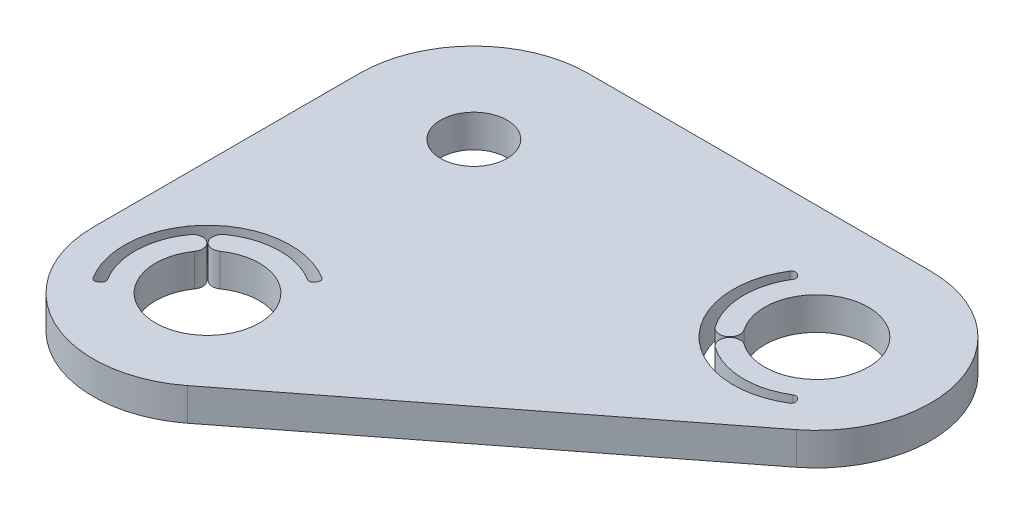
SolidWorks part; units mm, degrees
ref_plane "Front" through (0, 0, 0) normal (0, 0, 1) x (1, 0, 0)
ref_plane "Top" through (0, 0, 0) normal (0, 1, 0) x (1, 0, 0)
ref_plane "Right" through (0, 0, 0) normal (1, 0, 0) x (0, 0, -1)
sketch "Sketch2" plane through (0, 0, 0) normal (0, 1, 0) x (1, 0, 0)
  line L0 (0, 0) -> (0, 12.825) construction
  line L1 (0, 12.825) -> (16.5, 12.825) construction
  line L2 (-5.5, -11.241) -> (32.5382, 18.325) construction
  line L3 (32.5382, 18.325) -> (-5.5, 18.325) construction
  line L4 (-5.5, 18.325) -> (-5.5, -11.241) construction
  line L5 (-5.5, 0) -> (-5.5, 12.825)
  line L6 (0, 18.325) -> (16.5, 18.325)
  line L7 (19.8753, 8.4825) -> (3.3753, -4.3425)
  circle A0 centre (0, 12.825) radius 1.6
  circle A1 centre (16.5, 12.825) radius 2.5
  circle A2 centre (0, 0) radius 2.5
  circle A3 centre (16.5, 12.825) radius 5.5 construction
  circle A4 centre (0, 12.825) radius 5.5 construction
  circle A5 centre (0, 0) radius 5.5 construction
  arc A6 (-5.5, 12.825) -> (0, 18.325) centre (0, 12.825) cw
  arc A7 (16.5, 18.325) -> (19.8753, 8.4825) centre (16.5, 12.825) cw
  arc A8 (3.3753, -4.3425) -> (-5.5, 0) centre (0, 0) cw
  dimension "D3" = 5
  dimension "D4" = 3.2
  dimension "D5" = 3
  dimension "D1" = 12.825
  dimension "D2" = 16.5
extrude "Boss-Extrude1" add sketch "Sketch2" along normal blind 1.57
other "Move Face1" [suppressed] offset 0.0762 parameters "D1"=0.0762
sketch "Sketch3" [suppressed] plane through (0, 1.57, 0) normal (0, 1, 0) x (1, 0, 0)
  line L3 (3.3753, -4.3425) -> (19.8753, 8.4825)
  line L4 (16.5, 18.325) -> (0, 18.325)
  line L5 (-5.5, 12.825) -> (-5.5, 0)
  line L6 (3.3753, -4.3425) -> (19.8753, 8.4825)
  line L7 (16.5, 18.325) -> (0, 18.325)
  line L8 (-5.5, 12.825) -> (-5.5, 0)
  circle A0 centre (0, 0) radius 2.5 construction
  circle A1 centre (16.5, 12.825) radius 2.5 construction
  circle A2 centre (0, 12.825) radius 1.6 construction
  arc A3 (-5.5, 0) -> (3.3753, -4.3425) centre (0, 0) ccw
  arc A4 (19.8753, 8.4825) -> (16.5, 18.325) centre (16.5, 12.825) ccw
  arc A5 (0, 18.325) -> (-5.5, 12.825) centre (0, 12.825) ccw
  arc A6 (-5.5, 0) -> (3.3753, -4.3425) centre (0, 0) ccw
  arc A7 (19.8753, 8.4825) -> (16.5, 18.325) centre (16.5, 12.825) ccw
  arc A8 (0, 18.325) -> (-5.5, 12.825) centre (0, 12.825) ccw
  circle A9 centre (0, 0) radius 2.5
  circle A10 centre (16.5, 12.825) radius 2.5
  circle A11 centre (0, 12.825) radius 1.6
  dimension "D1" = 0
extrude "Boss-Extrude2" [suppressed] add sketch "Sketch3" along normal blind 2.83
sketch "Sketch4" [suppressed] plane through (0, 4.4, 0) normal (0, 1, 0) x (1, 0, 0)
  circle A8 centre (0, 12.825) radius 1.6 construction
  circle A9 centre (0, 12.825) radius 1.6
  circle A10 centre (0, 12.825) radius 5.5
  arc A11 (0, 18.325) -> (-5.5, 12.825) centre (0, 12.825) ccw construction
extrude "Boss-Extrude3" [suppressed] add sketch "Sketch4" along normal blind 0.6
sketch "Sketch5" plane through (0, 0, 0) normal (0, -1, 0) x (1, 0, 0)
  line B0 (13.4736, -14.9441) -> (13.3915, -15.0016)
  line B1 (18.6191, -9.7986) -> (18.6766, -9.7165)
  arc B2 (13.1072, -14.9437) -> (18.6187, -9.4322) centre (16.5, -12.825) cw
  arc B3 (14.4521, -11.3911) -> (13.633, -10.8175) centre (14.0425, -11.1043) ccw
  arc B4 (13.633, -10.8175) -> (13.5286, -14.6746) centre (16.5, -12.825) ccw
  arc B5 (14.4925, -9.958) -> (18.3496, -9.8536) centre (16.5, -12.825) cw
  arc B6 (15.0661, -10.7771) -> (14.4925, -9.958) centre (14.7793, -10.3675) cw
  arc B7 (14.4521, -11.3911) -> (15.0661, -10.7771) centre (16.5, -12.825) cw
  arc B8 (13.4736, -14.9441) -> (13.5286, -14.6746) centre (13.3589, -14.7803) ccw
  arc B9 (13.3915, -15.0016) -> (13.1072, -14.9437) centre (13.2768, -14.8377) cw
  arc B10 (18.6766, -9.7165) -> (18.6187, -9.4322) centre (18.5127, -9.6018) ccw
  arc B11 (18.6191, -9.7986) -> (18.3496, -9.8536) centre (18.4553, -9.6839) cw
  line B12 (2.1191, -3.0264) -> (2.1766, -3.1085)
  line B13 (-3.0264, 2.1191) -> (-3.1085, 2.1766)
  arc B14 (2.1187, -3.3928) -> (-3.3928, 2.1187) centre (0, 0) cw
  arc B15 (-1.4339, -2.0479) -> (-2.0075, -2.867) centre (-1.7207, -2.4575) ccw
  arc B16 (-2.0075, -2.867) -> (1.8496, -2.9714) centre (0, 0) ccw
  arc B17 (-2.867, -2.0075) -> (-2.9714, 1.8496) centre (0, 0) cw
  arc B18 (-2.0479, -1.4339) -> (-2.867, -2.0075) centre (-2.4575, -1.7207) cw
  arc B19 (-1.4339, -2.0479) -> (-2.0479, -1.4339) centre (0, 0) cw
  arc B20 (2.1191, -3.0264) -> (1.8496, -2.9714) centre (1.9553, -3.1411) ccw
  arc B21 (2.1766, -3.1085) -> (2.1187, -3.3928) centre (2.0127, -3.2232) cw
  arc B22 (-3.1085, 2.1766) -> (-3.3928, 2.1187) centre (-3.2232, 2.0127) ccw
  arc B23 (-3.0264, 2.1191) -> (-2.9714, 1.8496) centre (-3.1411, 1.9553) cw
sketch_block_instance "5mm_bore_flexure_relief-1"
sketch_block "5mm_bore_flexure_relief" parameters "D4"=2.5, "D6"=0.2, "D1"=80, "D2"=0.5, "D3"=70, "D5"=1
sketch_block_instance "5mm_bore_flexure_relief-2"
extrude "bore relief" cut sketch "Sketch5" against normal through all
mirror "Mirror3" [suppressed] of bodies 106 104
delete or keep bodies "Body-Delete/Keep 1" [suppressed] type keep bodies bodies 105
